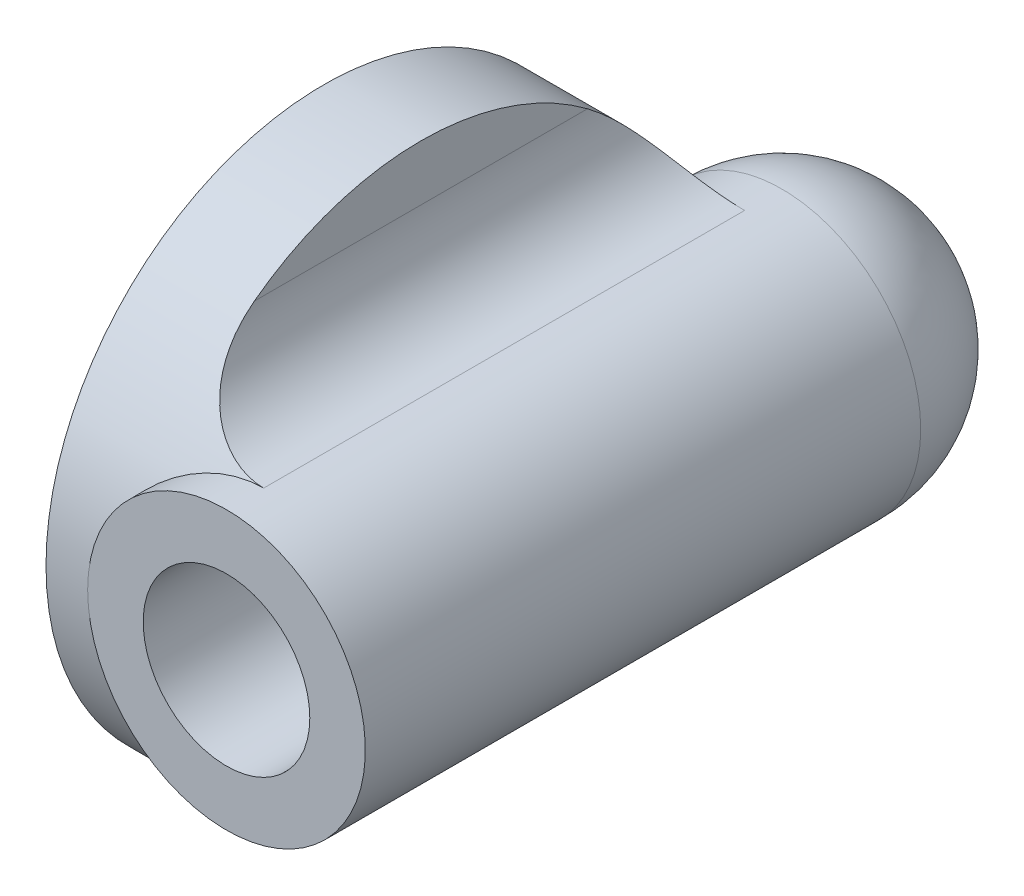
SolidWorks part; units mm, degrees
material "ABS PC"
ref_plane "Front Plane" through (0, 0, 0) normal (0, 0, 1) x (1, 0, 0)
ref_plane "Top Plane" through (0, 0, 0) normal (0, 1, 0) x (1, 0, 0)
ref_plane "Right Plane" through (0, 0, 0) normal (1, 0, 0) x (0, 0, -1)
sketch "Sketch1" plane through (0, 0, 0) normal (0, 0, 1) x (1, 0, 0)
  circle A0 centre (0, 0) radius 10
  circle A1 centre (0, 0) radius 6
  dimension "D1" = 20
  dimension "D2" = 12
extrude "Boss-Extrude1" add sketch "Sketch1" along normal blind 40
sketch "Sketch6" plane through (0, 0, 0) normal (0, 1, 0) x (1, 0, 0)
  line L0 (-10, 0) -> (0, 0)
  line L1 (0, 10) -> (0, 0)
  arc A0 (0, 10) -> (-10, 0) centre (0, 0) ccw
revolve "Revolve1" add sketch "Sketch6" angle 360 about L1
ref_plane "Plane1" through (-10, 0, 0) normal (-1, 0, 0) x (0, 0, 1)
sketch "Sketch7" plane through (-10, 0, 0) normal (-1, 0, 0) x (0, 0, 1)
  circle A0 centre (20, 0) radius 20
extrude "Boss-Extrude4" add sketch "Sketch7" along normal blind 3 and the other way blind 4
fillet "Fillet3" radius 6 2 edges at (-6, 8, 20) (-6, -8, 20)
sketch "Sketch8" plane through (-13, 0, 0) normal (-1, 0, 0) x (0, 0, 1)
  circle A0 centre (20, 0) radius 15
extrude "Cut-Extrude3" cut sketch "Sketch8" against normal blind 2
